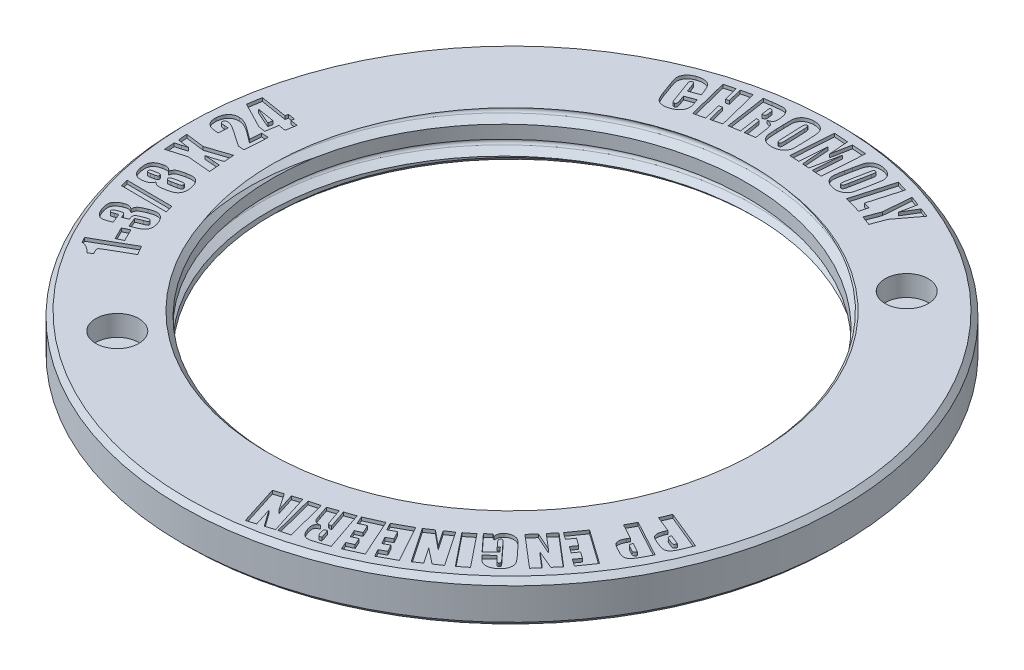
SolidWorks part; units mm, degrees
material "Chrome Stainless Steel"
ref_plane "Front" through (0, 0, 0) normal (0, 0, 1) x (1, 0, 0)
ref_plane "Top" through (0, 0, 0) normal (0, 1, 0) x (1, 0, 0)
ref_plane "Right" through (0, 0, 0) normal (1, 0, 0) x (0, 0, -1)
sketch "Sketch1" plane through (0, 0, 0) normal (0, 1, 0) x (1, 0, 0)
  circle A0 centre (0, 0) radius 25.2095
  circle A1 centre (0, 0) radius 18.3388
  dimension "D1" = 50.419
  dimension "D2" = 36.6776
extrude "Boss-Extrude1" add sketch "Sketch1" along normal mid plane 3.175
ref_plane "Plane1" through (0, 2.3495, 0) normal (0, 1, 0) x (1, 0, 0)
sketch "Sketch2" plane through (0, 2.3495, 0) normal (0, 1, 0) x (1, 0, 0)
  circle A0 centre (0, 0) radius 19.05
  dimension "D1" = 38.1
curve "Helix/Spiral1" pitch 2.1167 height 17.4625 radius 19.05 centre (0, 2.3495, 0) axis (0, -1, 0) start towards (0, 0, 1)
chamfer "Chamfer1" distance 0.381 angle 45 2 edges at (0, -1.5875, 18.3388) (0, 1.5875, 18.3388)
sketch "Sketch3" plane through (0, 0, 0) normal (1, 0, 0) x (0, 0, -1)
  line L0 (-18.923, 2.5695) -> (-17.78, 3.2294)
  line L1 (-17.78, 3.2294) -> (-17.78, 1.4696)
  line L2 (-17.78, 1.4696) -> (-18.923, 2.1295)
  line L3 (-17.78, 2.3495) -> (-19.304, 2.3495) construction
  arc A0 (-18.923, 2.5695) -> (-18.923, 2.1295) centre (-18.796, 2.3495) ccw
  point P7 (-19.05, 2.3495)
  dimension "D2" = 0.254
  dimension "D1" = 60
  dimension "D3" = 1.524
sweep "Cut-Sweep2" cut profiles "Sketch3" path "Helix/Spiral1" align with end faces yes
sketch "Sketch5" plane through (0, 1.5875, 0) normal (0, 1, 0) x (1, 0, 0)
  line L0 (0, 0) -> (0, 20.9423) construction
  arc A0 (-13.4615, 16.0427) -> (13.4615, 16.0427) centre (0, 0) cw construction
  text T0 "CHROMOLY" font "Impact" height 3.175
  dimension "D2" = 20.9423
  dimension "D1" = 80
extrude "Cut-Extrude1" cut sketch "Sketch5" against normal offset from surface (0.254 mm away) 0.254 up to face at (0, 1.5875, 25.2095)
sketch "Sketch6" plane through (0, 1.5875, 0) normal (0, 1, 0) x (1, 0, 0)
  line L0 (0, 0) -> (-20.6241, -3.6366) construction
  line L1 (0, 0) -> (0, 20.9423) construction
  arc A0 (-19.6793, 7.1627) -> (-16.0427, -13.4615) centre (0, 0) ccw construction
  arc A1 (13.4615, 16.0427) -> (-13.4615, 16.0427) centre (0, 0) ccw construction
  text T0 "1-3/8 X 24" font "Impact" height 3.175
  dimension "D1" = 60
  dimension "D2" = 100
extrude "Cut-Extrude2" cut sketch "Sketch6" against normal blind 0.254
sketch "Sketch7" plane through (0, 1.5875, 0) normal (0, 1, 0) x (1, 0, 0)
  line L0 (0, 0) -> (13.4615, -16.0427) construction
  line L1 (0, 0) -> (0, 20.9423) construction
  arc A0 (19.6793, -7.1627) -> (3.6366, -20.6241) centre (0, 0) cw construction
  arc A1 (13.4615, 16.0427) -> (-13.4615, 16.0427) centre (0, 0) ccw construction
  text T0 "PP ENGINEERING" font "Impact" height 3.175
  dimension "D1" = 60
  dimension "D2" = 140
extrude "Cut-Extrude3" cut sketch "Sketch7" against normal blind 0.254
sketch "Sketch8" plane through (0, 1.5875, 0) normal (0, 1, 0) x (1, 0, 0)
  line L0 (13.7757, 16.4173) -> (-13.7757, -16.4173) construction
  line L1 (0, 0) -> (0, 25.2095) construction
  circle A0 centre (0, 0) radius 21.4312 construction
  circle A1 centre (-13.7757, -16.4173) radius 1.651
  circle A2 centre (13.7757, 16.4173) radius 1.651
  circle A3 centre (0, 0) radius 25.2095 construction
  dimension "D1" = 42.8625
  dimension "D3" = 3.302
  dimension "D2" = 40
extrude "Cut-Extrude4" cut sketch "Sketch8" against normal blind 1.5875
chamfer "Chamfer2" distance 0.381 angle 45 2 edges at (0, -1.5875, 25.2095) (0, 1.5875, 25.2095)
equation "\"diameterMajor\"= 1.985'input"
equation "\"D1@Sketch1\"=\"diameterMajor\""
equation "\"thick\"= .125'input"
equation "\"pitchDiaMax\"= 1.444'input"
equation "\"D2@Sketch1\"=\"pitchDiaMax\""
equation "\"D1@Boss-Extrude1\"=\"thick\""
equation "\"helix\"= 1 / 12'input"
equation "\"D4@Helix/Spiral1\"=\"helix\""
equation "\"threadDiaMax\"= 1.5'input"
equation "\"D1@Sketch2\"=\"threadDiaMax\""
equation "\"D2@Sketch5\"= ( \"diameterMajor\" - \"threadDiaMax\" ) * 1.7"
equation "\"engravingCut\"= .01"
equation "\"D1@Cut-Extrude1\"=\"engravingCut\""
equation "\"D1@Cut-Extrude2\"=\"engravingCut\""
equation "\"D1@Cut-Extrude3\"=\"engravingCut\""
equation "\"spannerBoltCircle\"= 1.6875"
equation "\"spannerDOC\"= .0625"
equation "\"D1@Sketch8\"=\"spannerBoltCircle\""
equation "\"D1@Cut-Extrude4\"=\"spannerDOC\""
